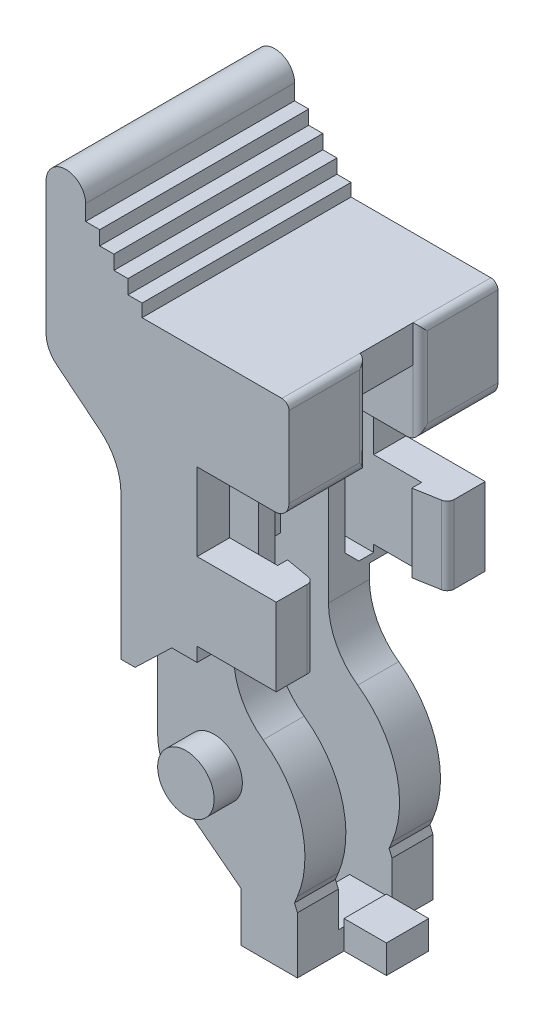
SolidWorks part; units mm, degrees
material "ABS"
ref_plane "Front" through (0, 0, 0) normal (0, 0, 1) x (1, 0, 0)
ref_plane "Top" through (0, 0, 0) normal (0, 1, 0) x (1, 0, 0)
ref_plane "Right" through (0, 0, 0) normal (1, 0, 0) x (0, 0, -1)
sketch "Sketch1" plane through (0, 0, 0) normal (0, 1, 0) x (1, 0, 0)
  line L1 (-0.75, -0.75) -> (0.75, -0.75)
  line L2 (-0.75, -0.75) -> (-0.75, 0.75)
  line L3 (-0.75, 0.75) -> (0.75, 0.75)
  line L4 (0.75, -0.75) -> (0.75, 0.75)
  line L5 (-0.75, -0.75) -> (0.75, 0.75) construction
  line L6 (-0.75, 0.75) -> (0.75, -0.75) construction
  point P0 (0, 0)
  dimension "D1" = 1.5
  dimension "D2" = 1.5
extrude "Base Block" add sketch "Sketch1" along normal blind 1
sketch "Sketch2" plane through (-0.75, 0, 0) normal (-1, 0, 0) x (0, 0, 1)
  line L0 (-0.75, 1) -> (0.75, 1) construction
  line L1 (2.4, 0.75) -> (-2.4, 0.75)
  line L2 (2.4, 0.75) -> (2.4, 0)
  line L3 (2.4, 0) -> (-2.4, 0)
  line L4 (-2.4, 0.75) -> (-2.4, 0)
  line L5 (2.4, 0.75) -> (-2.4, 0) construction
  line L6 (2.4, 0) -> (-2.4, 0.75) construction
  line L7 (-0.75, 0) -> (0.75, 0) construction
  point P0 (0, 0.375)
  dimension "D1" = 4.8
  dimension "D2" = 0.25
extrude "Base Bridge" add sketch "Sketch2" along normal blind 1.5
sketch "Positioning" plane through (0, 0, 0) normal (0, 0, 1) x (1, 0, 0)
  line L0 (-5.7, -2) -> (2, -2)
  line L1 (-5.7, -2) -> (-5.7, 8)
  line L2 (-0.75, 1) -> (0.75, 1) construction
  line L3 (0.75, 1) -> (0.75, 0) construction
  line L5 (-5.7, 2) -> (-4.45, 2)
  line L6 (-5.7, 2) -> (-5.7, -2)
  line L7 (-5.7, -2) -> (-4.45, -2)
  line L8 (-4.45, 2) -> (-4.45, -2)
  line L9 (-4.45, 0.1) -> (-3, 0.1)
  line L10 (-4.45, 0.1) -> (-4.45, -2)
  line L11 (-4.45, -2) -> (-3, -2)
  line L12 (-3, 0.1) -> (-3, -2)
  circle A0 centre (-3.7, 5) radius 1
  dimension "D1" = 7
  dimension "D2" = 2
  dimension "D3" = 2
  dimension "D4" = 3
  dimension "D5" = 7.7
  dimension "D6" = 1.25
  dimension "D7" = 4
  dimension "D8" = 1.25
  dimension "D9" = 2.7
  dimension "D10" = 2.1
  dimension "D11" = 10
sketch "Sketch5" plane through (0, 0, 2.4) normal (0, 0, 1) x (1, 0, 0)
  line L0 (-0.75, 0) -> (-2.75, 0)
  line L1 (-2.75, 0) -> (-2.75, 1.75)
  line L2 (-2.75, 1.75) -> (-4.9176, 3.4133)
  line L3 (-5.7, -2) -> (-5.7, 8) construction
  line L4 (-5.7, -2) -> (2, -2) construction
  line L5 (-5.7, 5) -> (-5.7, 14)
  line L6 (-0.2, 9.7) -> (-3, 9.7)
  line L7 (-5.7, 14) -> (-8.35, 16.15)
  line L8 (-8.35, 16.15) -> (-8.35, 21.3)
  line L9 (-8.35, 21.3) -> (-6.95, 21.3) construction
  line L10 (-6.95, 21.3) -> (-6.95, 18.8)
  line L11 (-6.95, 18.8) -> (0.25, 18.8)
  line L12 (0.25, 18.8) -> (0.25, 15.2)
  line L13 (0.25, 15.2) -> (-3, 15.2)
  line L14 (-3, 15.2) -> (-3, 12.45)
  line L15 (-3, 12.45) -> (-0.2, 12.45)
  line L16 (-0.2, 12.45) -> (-0.2, 9.7)
  line L17 (-3, 9.7) -> (-3, 8.7)
  line L18 (-3, 0.1) -> (-3, -2) construction
  line L19 (-0.75, 0) -> (-0.75, 2)
  line L21 (-0.75, 1) -> (0.75, 1) construction
  line L22 (-0.75, 2.5) -> (-0.8536, 2.25)
  line L23 (-0.75, 2) -> (-0.8536, 2.25)
  line L25 (-0.75, 2.5) -> (-0.75, 2) construction
  arc A0 (-4.9176, 3.4133) -> (-5.7, 5) centre (-3.7, 5) cw
  arc A1 (-8.35, 21.3) -> (-6.95, 21.3) centre (-7.65, 21.3) cw
  circle A4 centre (-3.7, 5) radius 1 construction
  arc A5 (-0.75, 2.5) -> (-1.9632, 6.6974) centre (-3.9836, 3.8394) ccw
  arc A6 (-1.9632, 6.6974) -> (-3, 8.7) centre (-0.5475, 8.7) cw
  point P13 (-5.7, 4.0137)
  dimension "D4" = 1
  dimension "D9" = 8.6
  dimension "D21" = 3.5
  dimension "D1" = 1.75
  dimension "D2" = 0.25
  dimension "D3" = 1
  dimension "D5" = 16
  dimension "D6" = 1.4
  dimension "D7" = 5.85
  dimension "D8" = 8
  dimension "D11" = 3.2
  dimension "D12" = 3.6
  dimension "D13" = 20.8
  dimension "D14" = 0.45
  dimension "D15" = 2.7
  dimension "D16" = 5.5
  dimension "D17" = 2.75
  dimension "D18" = 2.75
  dimension "D19" = 22.5
  dimension "D20" = 0.5
extrude "Lower Side 1" add sketch "Sketch5" against normal blind 1.45
sketch "Sketch6" plane through (0, 0, 2.4) normal (0, 0, 1) x (1, 0, 0)
  circle A0 centre (-3.7, 5) radius 1
  circle A1 centre (-3.7, 5) radius 1 construction
extrude "Pivot" add sketch "Sketch6" along normal blind 1
mirror "Lower Side 2" about plane through (0, 0, 0) normal (0, 0, 1) of "Pivot", "Lower Side 1"
sketch "Sketch7" plane through (0, 0, 0) normal (0, 0, 1) x (1, 0, 0)
  line L0 (-5.7, 14) -> (-5.7, 5) construction
  line L1 (-8.35, 16.15) -> (-5.7, 14) construction
  line L2 (-8.35, 21.3) -> (-8.35, 16.15) construction
  line L4 (0.25, 18.8) -> (-6.95, 18.8) construction
  line L5 (0.25, 15.2) -> (0.25, 18.8) construction
  line L6 (-3, 15.2) -> (0.25, 15.2) construction
  line L7 (-3, 12.45) -> (-3, 15.2) construction
  line L8 (-0.2, 12.45) -> (-3, 12.45) construction
  line L9 (-0.2, 9.7) -> (-0.2, 12.45) construction
  line L10 (-3, 9.7) -> (-0.2, 9.7) construction
  line L11 (-3, 8.7) -> (-3, 9.7) construction
  line L12 (-5.7, 14) -> (-5.7, 5) construction
  line L13 (-8.35, 16.15) -> (-5.7, 14)
  line L14 (-8.35, 21.3) -> (-8.35, 16.15)
  line L15 (-4.95, 18.8) -> (0.25, 18.8)
  line L16 (0.25, 18.8) -> (-6.95, 18.8) construction
  line L17 (0.25, 15.2) -> (0.25, 18.8)
  line L18 (-3, 15.2) -> (0.25, 15.2)
  line L19 (-3, 12.45) -> (-3, 15.2)
  line L20 (-0.2, 12.45) -> (-3, 12.45)
  line L21 (-0.2, 9.7) -> (-0.2, 12.45)
  line L22 (-3, 9.7) -> (-0.2, 9.7)
  line L23 (-3, 8.7) -> (-3, 9.7) construction
  line L24 (-3, 9.7) -> (-3, 9.2)
  line L25 (-3, 9.2) -> (-3.9, 9.2)
  line L26 (-3.9, 9.2) -> (-5.2, 7.95)
  line L27 (-5.2, 7.95) -> (-5.7, 7.95)
  line L28 (-5.7, 7.95) -> (-5.7, 14)
  line L29 (-8.35, 20.75) -> (0.25, 20.75) construction
  line L30 (-8.35, 20.25) -> (0.25, 20.25) construction
  line L31 (0.25, 20.75) -> (0.25, 18.8) construction
  line L33 (-8.35, 19.75) -> (0.25, 19.75) construction
  line L34 (0.25, 19.25) -> (-8.35, 19.25) construction
  line L35 (-6.95, 21.3) -> (-6.95, 20.75)
  line L36 (-6.95, 20.75) -> (-6.45, 20.75)
  line L37 (-6.45, 20.75) -> (-6.45, 20.25)
  line L38 (-6.45, 20.25) -> (-5.95, 20.25)
  line L39 (-5.95, 20.25) -> (-5.95, 19.75)
  line L40 (-5.95, 19.75) -> (-5.45, 19.75)
  line L41 (-5.45, 19.75) -> (-5.45, 19.25)
  line L42 (-5.45, 19.25) -> (-4.95, 19.25)
  line L43 (-4.95, 19.25) -> (-4.95, 18.8)
  arc A0 (-6.95, 21.3) -> (-8.35, 21.3) centre (-7.65, 21.3) ccw construction
  arc A1 (-6.95, 21.3) -> (-8.35, 21.3) centre (-7.65, 21.3) ccw
  dimension "D1" = 0.5
  dimension "D2" = 0.9
  dimension "D3" = 1.25
  dimension "D4" = 0.5
  dimension "D5" = 1.25
  dimension "D6" = 0.5
  dimension "D7" = 0.5
  dimension "D8" = 0.5
  dimension "D9" = 0.5
  dimension "D10" = 0.5
  dimension "D11" = 0.5
  dimension "D12" = 0.5
  dimension "D13" = 3.4
extrude "Body Block" add sketch "Sketch7" along normal mid plane 7.4
sketch "Sketch8" plane through (-5.7, 0, 0) normal (-1, 0, 0) x (0, 0, 1)
  line L0 (0, -2) -> (0, 8) construction
  line L1 (-0.95, 1.75) -> (0.95, 1.75)
  line L2 (-0.95, 1.75) -> (-0.95, 10)
  line L3 (-0.95, 10) -> (0.95, 10)
  line L4 (0.95, 1.75) -> (0.95, 10)
  line L5 (-0.95, 1.75) -> (0.95, 10) construction
  line L6 (-0.95, 10) -> (0.95, 1.75) construction
  line L7 (-0.95, 7.95) -> (-0.95, 5) construction
  line L8 (-0.95, 1.75) -> (-2.4, 1.75) construction
  point P0 (0, 5.875)
  dimension "D1" = 12
extrude "Rear Cut Through" cut sketch "Sketch8" against normal through all
sketch "Sketch9" plane through (0, 12.45, 0) normal (0, 1, 0) x (1, 0, 0)
  line L0 (-1.3, -2.2) -> (-0.4066, -2.3575)
  line L1 (-0.2, 3.7) -> (-0.2, -3.7) construction
  line L2 (-3, 2.55) -> (-1.3, 2.55)
  line L3 (-1.3, 2.55) -> (-1.3, 2.2)
  line L4 (-3, 2.55) -> (-3, -2.55)
  line L5 (0, 0) -> (-3, 0) construction
  line L6 (-1.3, 2.2) -> (-0.4066, 2.3575)
  line L7 (-3, -2.55) -> (-1.3, -2.55)
  line L8 (-1.3, -2.55) -> (-1.3, -2.2)
  line L9 (-0.2, -2.6037) -> (-0.2, -3.7) construction
  line L10 (-0.2, 2.6037) -> (-0.2, 3.7) construction
  line L11 (-0.2, 2.6037) -> (-0.2, -2.6037)
  line L12 (-3, 3.7) -> (-3, -3.7) construction
  arc A0 (-0.2, 2.6037) -> (-0.4066, 2.3575) centre (-0.45, 2.6037) cw
  arc A1 (-0.2, -2.6037) -> (-0.4066, -2.3575) centre (-0.45, -2.6037) ccw
  point P17 (-0.2, 2.394)
  dimension "D3" = 1.1
  dimension "D6" = 0.25
  dimension "D1" = 5.1
  dimension "D4" = 4.4
  dimension "D5" = 80
extrude "Clip Forming" cut sketch "Sketch9" against normal up to surface (2.75 mm away) up to face at (-1.6, 9.7, 2.325)
sketch "Sketch10" plane through (-3, 0, 0) normal (1, 0, 0) x (0, 0, -1)
  line L0 (0, 10) -> (0, 15.2) construction
  line L1 (0.95, 10) -> (-0.95, 10) construction
  line L2 (3.7, 15.2) -> (-3.7, 15.2) construction
  line L3 (1.5265, 14.45) -> (1.5265, 9.45) construction
  line L4 (-2.55, 14.45) -> (-1.5265, 14.45)
  line L5 (-2.55, 14.45) -> (-2.55, 9.45)
  line L6 (-2.55, 9.45) -> (-1.5265, 9.45) construction
  line L7 (-1.5265, 14.45) -> (-1.5265, 9.45) construction
  line L8 (2.55, 9.45) -> (1.5265, 9.45) construction
  line L9 (2.55, 14.45) -> (2.55, 9.45)
  line L10 (2.55, 14.45) -> (1.5265, 14.45)
  line L11 (-2.55, 9.7) -> (-2.55, 12.45) construction
  line L12 (-3.7, 7.95) -> (-2.4, 7.95) construction
  line L13 (-1.5265, 9.95) -> (-2.0265, 9.45)
  line L14 (-2.55, 9.45) -> (-2.0265, 9.45)
  line L15 (-1.5265, 9.95) -> (-1.5265, 14.45)
  line L16 (2.55, 9.45) -> (2.0265, 9.45)
  line L17 (1.5265, 9.95) -> (2.0265, 9.45)
  line L18 (1.5265, 9.95) -> (1.5265, 14.45)
  line L20 (3.7, 15.2) -> (-3.7, 15.2) construction
  dimension "D1" = 1.5
  dimension "D2" = 3.053
  dimension "D3" = 0.5
  dimension "D4" = 0.5
  dimension "D5" = 0.75
extrude "Through Holes" cut sketch "Sketch10" against normal through all
sketch "Sketch11" plane through (0.25, 0, 0) normal (1, 0, 0) x (0, 0, -1)
  line L0 (3.7, 18.8) -> (-3.7, 18.8) construction
  line L1 (-0.95, 17.5) -> (0.95, 17.5)
  line L2 (-0.95, 17.5) -> (-0.95, 10)
  line L3 (-0.95, 10) -> (0.95, 10)
  line L4 (0.95, 17.5) -> (0.95, 10)
  dimension "D1" = 1.3
extrude "PCB Slot" cut sketch "Sketch11" against normal offset from surface (4.95 mm away) 1 up to face at (-5.7, 9.7045, 0)
sketch "Sketch13" plane through (0, 0, -2.55) normal (0, 0, 1) x (1, 0, 0)
  line L0 (-8.35, 20.2) -> (-4, 16.5)
  line L2 (-4, 16.5) -> (-4, 14.45)
  line L4 (-8.35, 21.3) -> (-8.35, 16.15) construction
  line L6 (-6.2547, 14.45) -> (-3, 14.45) construction
  line L7 (-4, 14.45) -> (-6.2547, 14.45)
  line L8 (-6.2547, 14.45) -> (-8.35, 16.15)
  line L9 (-8.35, 16.15) -> (-8.35, 20.2)
  line L10 (-3, 12.45) -> (-3, 14.45) construction
  line L11 (-8.35, 16.15) -> (-5.7, 14) construction
  arc A2 (-6.95, 21.3) -> (-8.35, 21.3) centre (-7.65, 21.3) ccw construction
  dimension "D1" = 5.5
  dimension "D2" = 1.8
  dimension "D3" = 1
extrude "Through Hole Rear 1" cut sketch "Sketch13" along normal up to surface (1.0235 mm away) up to face at (-4.7309, 12.56, -1.5265)
sketch "Sketch14" plane through (0, 0, 2.55) normal (0, 0, -1) x (-1, 0, 0)
  line L5 (8.35, 20.2) -> (4, 16.5)
  line L6 (4, 16.5) -> (4, 14.45)
  line L7 (4, 14.45) -> (6.2547, 14.45)
  line L8 (6.2547, 14.45) -> (8.35, 16.15)
  line L9 (8.35, 16.15) -> (8.35, 20.2)
  line L10 (8.35, 20.2) -> (4, 16.5)
  line L11 (4, 16.5) -> (4, 14.45)
  line L12 (4, 14.45) -> (6.2547, 14.45)
  line L13 (6.2547, 14.45) -> (8.35, 16.15)
  line L14 (8.35, 16.15) -> (8.35, 20.2)
  dimension "D1" = 0
extrude "Through Hole Rear 2" cut sketch "Sketch14" along normal up to surface (1.0235 mm away) up to face at (-4.7309, 12.56, 1.5265)
sketch "Sketch15" plane through (0.25, 0, 0) normal (1, 0, 0) x (0, 0, -1)
  line L0 (3.7, 18.8) -> (-3.7, 18.8) construction
  line L1 (-0.95, 17.5) -> (0.95, 17.5)
  line L2 (-0.95, 17.5) -> (-0.95, 18.8)
  line L3 (-0.95, 18.8) -> (0.95, 18.8)
  line L4 (0.95, 17.5) -> (0.95, 18.8)
  line L5 (0.95, 10) -> (0.95, 17.5) construction
extrude "PCB Slot Top" cut sketch "Sketch15" against normal blind 0.25
fillet "Rear Fillet (2mm)" radius 2 3 edges at (-5.7, 14, 3.125) (-5.7, 14, -3.125) (-5.7, 14, 0)
fillet "Rear Fillet (1mm)" radius 1 3 edges at (-8.35, 16.15, -3.125) (-8.35, 16.15, 0) (-8.35, 16.15, 3.125)
fillet "Guide Fillet (0.25mm)" radius 0.25 6 edges at (0.25, 17, -0.95) (0.25, 17, 0.95) (0.25, 18.8, -2.325) (0.25, 18.8, 2.325) (0.125, 18.8, 0.95) (0.125, 18.8, -0.95)
fillet "Guide Fillet (0.5mm)" radius 0.5 1 edges at (0.25, 15.2, 2.45)
